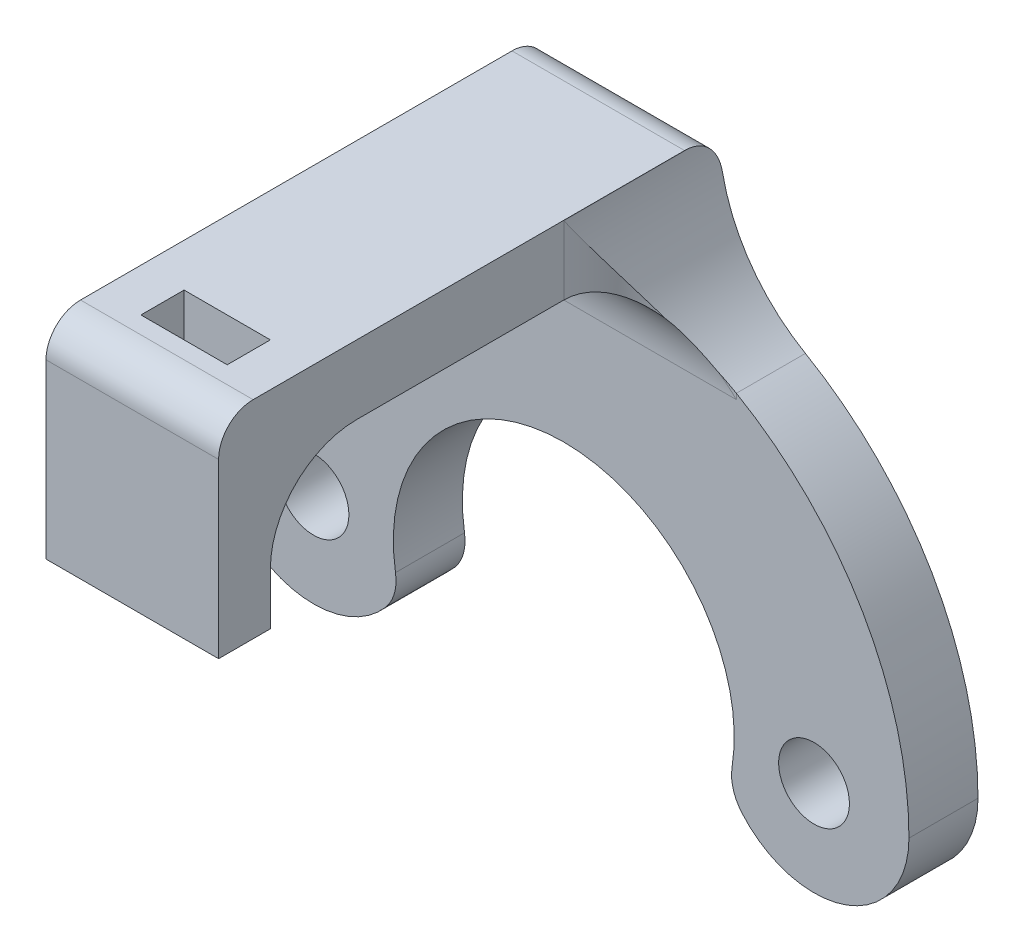
SolidWorks part; units mm, degrees
ref_plane "Alzado" through (0, 0, 0) normal (0, 0, 1) x (1, 0, 0)
ref_plane "Planta" through (0, 0, 0) normal (0, 1, 0) x (1, 0, 0)
ref_plane "Vista lateral" through (0, 0, 0) normal (1, 0, 0) x (0, 0, -1)
sketch "Croquis1" plane through (0, 0, 0) normal (0, 0, 1) x (1, 0, 0)
  line L0 (0, 21) -> (0, 0) construction
  circle A1 centre (14.5, 0) radius 1.9 construction
  circle A2 centre (-14.5, 0) radius 1.9 construction
  circle A3 centre (14.5, 0) radius 1.9 construction
  circle A4 centre (-14.5, 0) radius 1.9 construction
  circle A5 centre (-14.5, 0) radius 2.05
  circle A6 centre (14.5, 0) radius 2.05
  arc A7 (20, 0) -> (-20, 0) centre (0, 0) ccw
  circle A8 centre (0, 0) radius 21 construction
  arc A9 (0, 21) -> (-21, 0) centre (0, 0) ccw construction
  circle A10 centre (0, 0) radius 8.875 construction
  circle A11 centre (0, 0) radius 8.875 construction
  arc A12 (9.7516, -1.5562) -> (-9.7516, -1.5562) centre (0, 0) ccw
  circle A13 centre (0, 0) radius 9.875 construction
  arc A15 (-10.3207, -3.5754) -> (-9.7516, -1.5562) centre (-12.2204, -1.9502) ccw
  arc A16 (0, 20) -> (-20, 0) centre (0, 0) ccw construction
  arc A17 (-20, 0) -> (-10.3207, -3.5754) centre (-14.5, 0) ccw
  circle A18 centre (14.5, 0) radius 1.9 construction
  arc A19 (20, 0) -> (10.3207, -3.5754) centre (14.5, 0) cw
  arc A20 (10.3207, -3.5754) -> (9.7516, -1.5562) centre (12.2204, -1.9502) cw
  circle A21 centre (14.5, 0) radius 2.05
  dimension "D1" = 4.1
  dimension "D3" = 2.5
  dimension "D2" = 1
  dimension "D4" = 1
extrude "Saliente-Extruir1" add sketch "Croquis1" along normal blind 4 contours A20 A19 A7 A17 A15 A12 A6 A5 region at (16.2414, -4.7143, 0)
sketch "Croquis2" plane through (0, 0, 4) normal (0, 0, 1) x (1, 0, 0)
  line L0 (0, 26) -> (0, 0) construction
  line L1 (-5, 26) -> (5, 26)
  line L2 (-5, 26) -> (-5, 19.3649)
  line L4 (5, 26) -> (5, 19.3649)
  line L5 (0, 20) -> (-5, 20) construction
  arc A0 (20, 0) -> (-20, 0) centre (0, 0) ccw construction
  arc A1 (5, 19.3649) -> (-5, 19.3649) centre (0, 0) ccw
  point P12 (5, 19.3649)
  point P13 (-5, 19.3649)
  dimension "D1" = 6
  dimension "D2" = 10
extrude "Saliente-Extruir3" add sketch "Croquis2" against normal up to vertex (4 mm away) up to point (20, 0, 0)
sketch "Croquis3" plane through (0, 0, 4) normal (0, 0, 1) x (1, 0, 0)
  line L0 (5, 19.3649) -> (5, 26) construction
  line L1 (-5, 26) -> (5, 26)
  line L2 (-5, 26) -> (-5, 22)
  line L3 (-5, 22) -> (5, 22)
  line L4 (5, 26) -> (5, 22)
  dimension "D1" = 4
extrude "Saliente-Extruir4" add sketch "Croquis3" along normal blind 26 from surface starting at face at (0, 9.016, 0)
sketch "Croquis4" plane through (0, 26, 0) normal (0, 1, 0) x (1, 0, 0)
  line L0 (5, 0) -> (5, -26) construction
  line L1 (-5, -26) -> (5, -26)
  line L2 (-5, -26) -> (-5, -29)
  line L3 (-5, -29) -> (5, -29)
  line L4 (5, -26) -> (5, -29)
  dimension "D1" = 3
extrude "Saliente-Extruir5" add sketch "Croquis4" against normal blind 12
fillet "Redondeo1" radius 10 2 edges at (-5, 19.3649, 2) (5, 19.3649, 2)
fillet "Redondeo2" radius 5 3 edges at (5, 23.9904, 4) (-5, 23.9904, 4) (0, 22, 4)
sketch "Croquis5" plane through (0, 22, 0) normal (0, -1, 0) x (1, 0, 0)
  line L0 (-5, 26) -> (5, 26) construction
  line L1 (-2.5, 26) -> (2.5, 26)
  line L2 (-2.5, 26) -> (-2.5, 23.5)
  line L3 (-2.5, 23.5) -> (2.5, 23.5)
  line L4 (2.5, 26) -> (2.5, 23.5)
  line L5 (0, 29) -> (0, 23.5) construction
  line L6 (-5, 29) -> (5, 29) construction
  dimension "D1" = 2.5
  dimension "D2" = 5
extrude "Cortar-Extruir1" cut sketch "Croquis5" against normal up to next
fillet "Redondeo4" radius 5 1 edges at (3.75, 22, 26)
fillet "Redondeo5" radius 2 2 edges at (0, 26, 29) (0, 26, 0)
